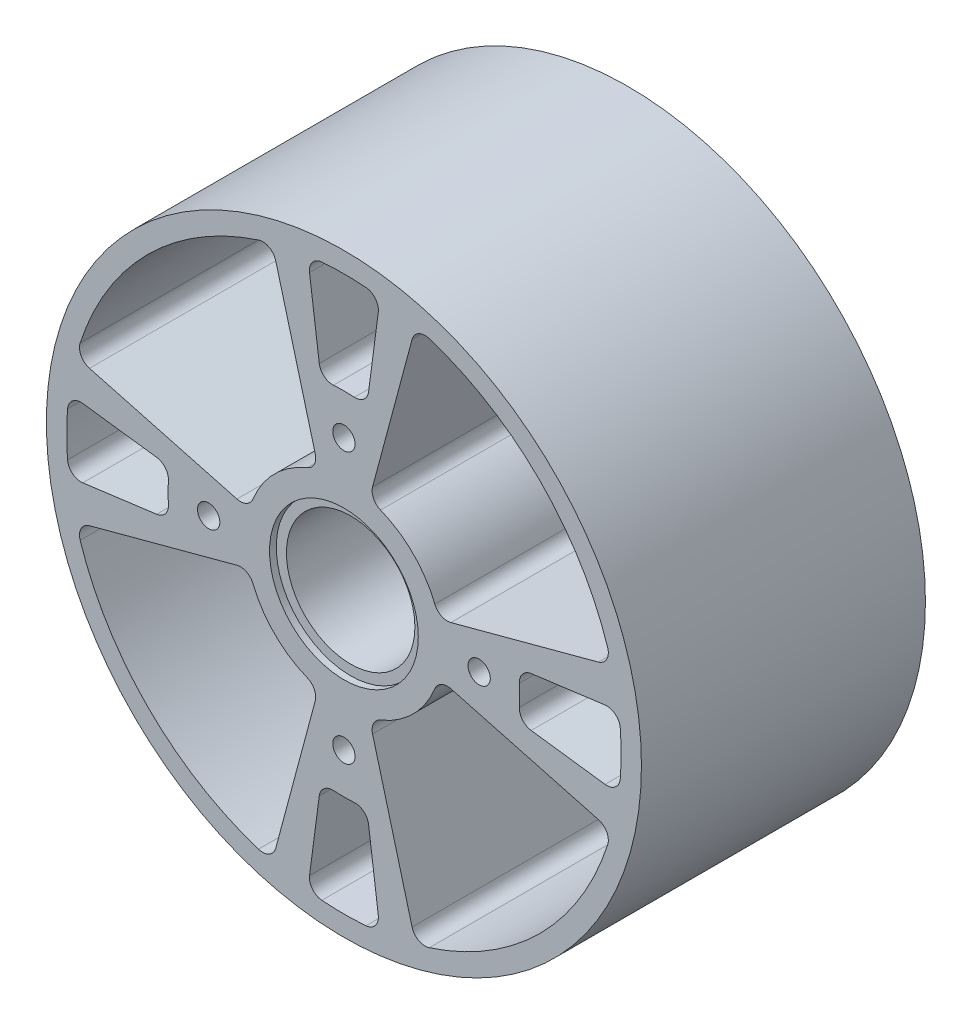
SolidWorks part; units mm, degrees
material "3.0205 (EN-AW 1200)"
ref_plane "前视基准面" through (0, 0, 0) normal (0, 0, 1) x (1, 0, 0)
ref_plane "上视基准面" through (0, 0, 0) normal (0, 1, 0) x (1, 0, 0)
ref_plane "右视基准面" through (0, 0, 0) normal (1, 0, 0) x (0, 0, -1)
sketch "草图1" plane through (0, 0, 0) normal (0, 0, 1) x (1, 0, 0)
  circle A0 centre (0, 0) radius 41
  circle A1 centre (0, 0) radius 44
  dimension "D1" = 82
  dimension "D2" = 3
extrude "凸台-拉伸1" add sketch "草图1" along normal blind 6
sketch "草图2" plane through (0, 0, 6) normal (0, 0, 1) x (1, 0, 0)
  circle A0 centre (0, 0) radius 44
  circle A1 centre (0, 0) radius 44 construction
extrude "凸台-拉伸2" add sketch "草图2" along normal blind 36
sketch "草图3" plane through (0, 0, 42) normal (0, 0, 1) x (1, 0, 0)
  circle A0 centre (0, 0) radius 44
  circle A1 centre (0, 0) radius 39
  circle A2 centre (0, 0) radius 44 construction
  dimension "D1" = 5
extrude "凸台-拉伸3" add sketch "草图3" along normal blind 10
sketch "草图4" plane through (0, 0, 42) normal (0, 0, 1) x (1, 0, 0)
  line L0 (0, 0) -> (-2.4588, 9.1763) construction
  line L1 (0, 0) -> (0, 44) construction
  line L2 (0, 0) -> (2.4588, 9.1763) construction
  line L3 (3.7529, 14.0059) -> (10.6116, 39.603)
  line L4 (2.4588, 9.1763) -> (3.7529, 14.0059) construction
  line L5 (-3.7529, 14.0059) -> (-10.6116, 39.603)
  line L6 (-2.4588, 9.1763) -> (-3.7529, 14.0059) construction
  line L7 (14.0059, -3.7529) -> (39.603, -10.6116)
  line L8 (14.0059, 3.7529) -> (39.603, 10.6116)
  line L9 (-3.7529, -14.0059) -> (-10.6116, -39.603)
  line L10 (3.7529, -14.0059) -> (10.6116, -39.603)
  line L11 (-14.0059, 3.7529) -> (-39.603, 10.6116)
  line L12 (-14.0059, -3.7529) -> (-39.603, -10.6116)
  line L13 (0, 0) -> (3.7529, 14.0059) construction
  circle A0 centre (0, 0) radius 9.5
  arc A1 (3.7529, -14.0059) -> (14.0059, -3.7529) centre (0, 0) ccw
  arc A2 (-39.603, -10.6116) -> (-10.6116, -39.603) centre (0, 0) ccw
  circle A3 centre (0, 0) radius 44 construction
  arc A4 (-39.603, 10.6116) -> (-39.603, -10.6116) centre (0, 0) ccw construction
  arc A5 (39.603, 10.6116) -> (10.6116, 39.603) centre (0, 0) ccw
  arc A6 (39.603, -10.6116) -> (39.603, 10.6116) centre (0, 0) ccw construction
  arc A7 (-10.6116, 39.603) -> (-39.603, 10.6116) centre (0, 0) ccw
  arc A8 (0, 41) -> (-10.6116, 39.603) centre (0, 0) ccw construction
  arc A9 (10.6116, 39.603) -> (0, 41) centre (0, 0) ccw construction
  arc A10 (10.6116, -39.603) -> (39.603, -10.6116) centre (0, 0) ccw
  arc A11 (-10.6116, -39.603) -> (10.6116, -39.603) centre (0, 0) ccw construction
  arc A12 (-3.7529, -14.0059) -> (3.7529, -14.0059) centre (0, 0) ccw construction
  arc A13 (14.0059, 3.7529) -> (3.7529, 14.0059) centre (0, 0) ccw
  arc A14 (14.0059, -3.7529) -> (14.0059, 3.7529) centre (0, 0) ccw construction
  arc A15 (-3.7529, 14.0059) -> (-14.0059, 3.7529) centre (0, 0) ccw
  arc A16 (0, 14.5) -> (-3.7529, 14.0059) centre (0, 0) ccw construction
  arc A17 (3.7529, 14.0059) -> (0, 14.5) centre (0, 0) ccw construction
  arc A18 (-14.0059, -3.7529) -> (-3.7529, -14.0059) centre (0, 0) ccw
  arc A19 (-14.0059, 3.7529) -> (-14.0059, -3.7529) centre (0, 0) ccw construction
  dimension "D1" = 19
  dimension "D2" = 82
  dimension "D3" = 5
  dimension "D4" = 30
extrude "切除-拉伸1" cut sketch "草图4" against normal up to next
fillet "圆角1" radius 2 16 edges at (14.0059, 3.7529, 24) (3.7529, 14.0059, 24) (10.6116, 39.603, 24) (39.603, 10.6116, 24) (-3.7529, 14.0059, 24) (-14.0059, 3.7529, 24) (-39.603, 10.6116, 24) (3.7529, -14.0059, 24) (14.0059, -3.7529, 24) (39.603, -10.6116, 24) (10.6116, -39.603, 24) (-14.0059, -3.7529, 24) (-3.7529, -14.0059, 24) (-10.6116, -39.603, 24) (-39.603, -10.6116, 24) (-10.6116, 39.603, 24)
sketch "草图8" plane through (0, 0, 42) normal (0, 0, 1) x (1, 0, 0)
  line L0 (0, 0) -> (0, 20) construction
  circle A0 centre (0, 0) radius 20 construction
  circle A1 centre (0, 20) radius 1.65
  circle A2 centre (20, 0) radius 1.65
  circle A3 centre (0, -20) radius 1.65
  circle A4 centre (-20, 0) radius 1.65
  dimension "D1" = 40
  dimension "D2" = 3.3
extrude "切除-拉伸5" cut sketch "草图8" against normal up to next
cosmetic thread "装饰螺纹线1" parameters "D2"=4
cosmetic thread "装饰螺纹线2" parameters "D2"=4
cosmetic thread "装饰螺纹线3" parameters "D2"=4
cosmetic thread "装饰螺纹线4" parameters "D2"=4
sketch "草图9" plane through (0, 0, 52) normal (0, 0, 1) x (1, 0, 0)
  circle A0 centre (0, 0) radius 44
  circle A1 centre (0, 0) radius 44 construction
extrude "切除-拉伸6" cut sketch "草图9" against normal blind 10
sketch "草图12" plane through (0, 0, 42) normal (0, 0, 1) x (1, 0, 0)
  line L0 (-3.3937, 25.7776) -> (-5.3516, 40.6492)
  line L1 (0, 0) -> (0, 41) construction
  line L2 (3.3937, 25.7776) -> (5.3516, 40.6492)
  line L3 (0, 0) -> (-3.3937, 25.7776) construction
  line L4 (0, 0) -> (3.3937, 25.7776) construction
  line L5 (25.7776, 3.3937) -> (40.6492, 5.3516)
  line L6 (25.7776, -3.3937) -> (40.6492, -5.3516)
  line L7 (3.3937, -25.7776) -> (5.3516, -40.6492)
  line L8 (-3.3937, -25.7776) -> (-5.3516, -40.6492)
  line L9 (-25.7776, -3.3937) -> (-40.6492, -5.3516)
  line L10 (-25.7776, 3.3937) -> (-40.6492, 5.3516)
  arc A0 (3.3937, 25.7776) -> (-3.3937, 25.7776) centre (0, 0) ccw
  arc A1 (5.3516, 40.6492) -> (-5.3516, 40.6492) centre (0, 0) ccw
  arc A2 (39.0067, 12.6285) -> (12.6285, 39.0067) centre (0, 0) ccw construction
  arc A3 (-3.3937, 25.7776) -> (3.3937, 25.7776) centre (0, 0) ccw construction
  arc A4 (-5.3516, 40.6492) -> (5.3516, 40.6492) centre (0, 0) ccw construction
  arc A5 (40.6492, -5.3516) -> (40.6492, 5.3516) centre (0, 0) ccw
  arc A6 (25.7776, -3.3937) -> (25.7776, 3.3937) centre (0, 0) ccw
  arc A7 (-5.3516, -40.6492) -> (5.3516, -40.6492) centre (0, 0) ccw
  arc A8 (-3.3937, -25.7776) -> (3.3937, -25.7776) centre (0, 0) ccw
  arc A9 (-40.6492, 5.3516) -> (-40.6492, -5.3516) centre (0, 0) ccw
  arc A10 (-25.7776, 3.3937) -> (-25.7776, -3.3937) centre (0, 0) ccw
  point P25 (0, 0)
  dimension "D1" = 15
  dimension "D2" = 15
  dimension "D3" = 4
extrude "切除-拉伸7" cut sketch "草图12" against normal up to next
sketch "草图13" plane through (0, 0, 42) normal (0, 0, 1) x (1, 0, 0)
  circle A0 centre (0, 0) radius 11
  dimension "D1" = 22
extrude "切除-拉伸8" cut sketch "草图13" against normal blind 1
fillet "圆角2" radius 2 16 edges at (-3.3937, 25.7776, 24) (-5.3516, 40.6492, 24) (-40.6492, 5.3516, 24) (-25.7776, 3.3937, 24) (-25.7776, -3.3937, 24) (-40.6492, -5.3516, 24) (-5.3516, -40.6492, 24) (-3.3937, -25.7776, 24) (3.3937, -25.7776, 24) (5.3516, -40.6492, 24) (40.6492, -5.3516, 24) (25.7776, -3.3937, 24) (25.7776, 3.3937, 24) (5.3516, 40.6492, 24) (3.3937, 25.7776, 24) (40.6492, 5.3516, 24)
